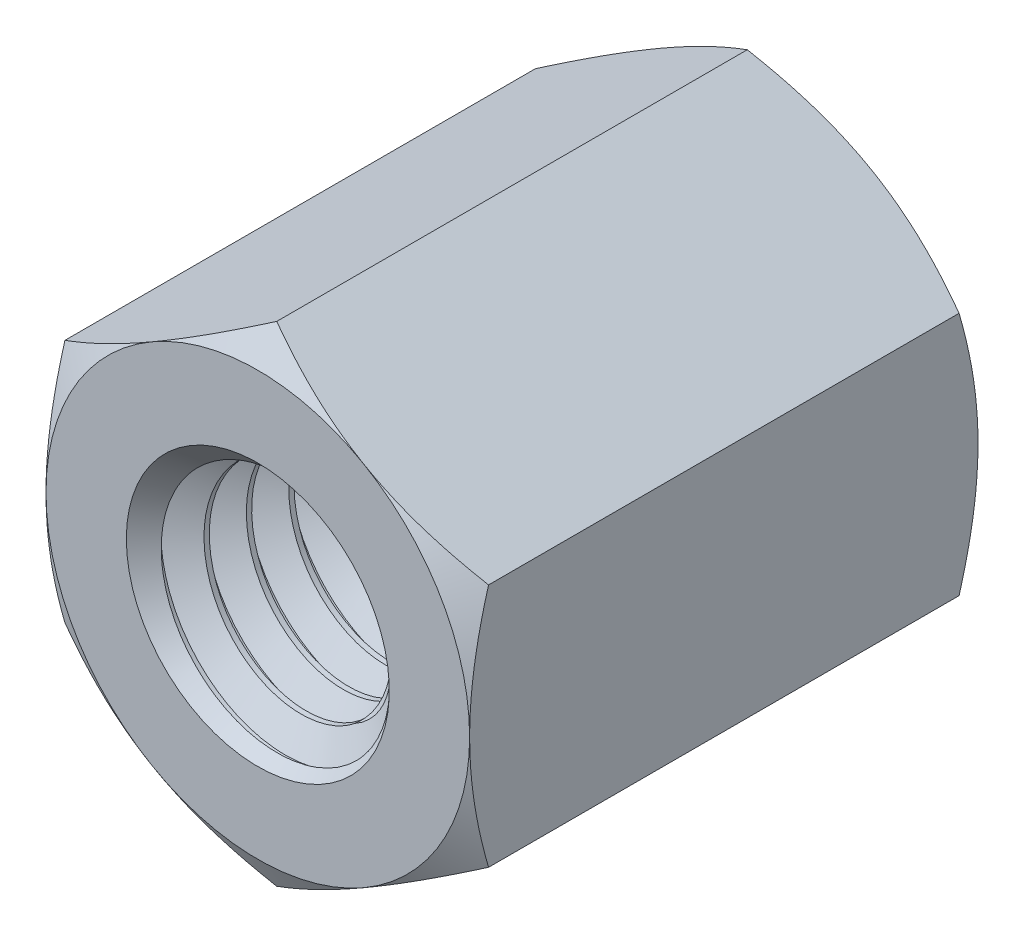
SolidWorks part; units mm, degrees
ref_plane "Front Plane" through (0, 0, 0) normal (0, 0, 1) x (1, 0, 0)
ref_plane "Top Plane" through (0, 0, 0) normal (0, 1, 0) x (1, 0, 0)
ref_plane "Right Plane" through (0, 0, 0) normal (1, 0, 0) x (0, 0, -1)
sketch "Sketch3" plane through (0, 0, 0) normal (1, 0, 0) x (0, 0, -1)
  line L0 (-4.7625, 0) -> (4.7625, 0) construction
  line L1 (0, 3.9688) -> (0, -3.9688) construction
  line L2 (-4.7625, 2.413) -> (-4.7625, -2.413) construction
  point P2 (-7.9375, 0)
  point P3 (7.9375, 0)
  dimension "Length" = 9.525
  dimension "Min Thread Length" = 12.7
  dimension "D1" = 12.7
  dimension "Thread Dia" = 4.826
  dimension "Hex" = 7.9375
sketch "Sketch1" plane through (0, 0, 0) normal (0, 0, 1) x (1, 0, 0)
  line L1 (0, 4.5827) -> (-3.9688, 2.2914)
  line L2 (-3.9688, 2.2914) -> (-3.9688, -2.2914)
  line L3 (-3.9688, -2.2914) -> (0, -4.5827)
  line L4 (0, -4.5827) -> (3.9688, -2.2914)
  line L5 (3.9688, -2.2914) -> (3.9688, 2.2914)
  line L6 (3.9688, 2.2914) -> (0, 4.5827)
  circle A0 centre (0, 0) radius 3.9688 construction
  circle A1 centre (0, 0) radius 2.413
extrude "Extrude1" add sketch "Sketch1" along normal up to vertex (4.7625 mm away) and the other way up to vertex (4.7625 mm away) up to point (0, 0, 4.7625) other way up to point (0, 0, -4.7625)
sketch "Sketch11" plane through (0, 0, -4.7625) normal (0, 0, -1) x (-1, 0, 0)
  circle A0 centre (0, 0) radius 2.413 construction
  circle A1 centre (0, 0) radius 2.413
curve "Helix/Spiral1" pitch 0.7937 height 10.3188 radius 2.413 centre (0, 0, -4.7625) axis (0, 0, 1) start towards (0, 1, 0) parameters "Pitch"=0.7937
sketch "Sketch12" plane through (0, 0, 0) normal (1, 0, 0) x (0, 0, -1)
  line L0 (5.457, 2.413) -> (4.7625, 2.413)
  line L1 (5.457, 2.413) -> (5.1594, 1.8974)
  line L2 (5.1594, 1.8974) -> (5.0602, 1.8974)
  line L3 (5.0602, 1.8974) -> (4.7625, 2.413)
  line L4 (5.1098, 1.8974) -> (5.1098, 2.413) construction
  line L5 (5.3082, 2.1552) -> (4.9113, 2.1552) construction
  dimension "D1" = 0.0992
  dimension "D2" = 0.3969
  dimension "D3" = 60
sweep "Sweep1" add profiles "Sketch12" path "Helix/Spiral1"
sketch "Sketch6" plane through (0, 0, -4.7625) normal (0, 0, -1) x (-1, 0, 0)
  line L6 (0, 4.5827) -> (-3.9688, 2.2914)
  line L7 (-3.9688, 2.2914) -> (-3.9688, -2.2914)
  line L8 (-3.9688, -2.2914) -> (0, -4.5827)
  line L9 (0, -4.5827) -> (3.9688, -2.2914)
  line L10 (3.9688, -2.2914) -> (3.9688, 2.2914)
  line L11 (3.9688, 2.2914) -> (0, 4.5827)
  line L12 (0, 4.5827) -> (-3.9688, 2.2914)
  line L13 (-3.9688, 2.2914) -> (-3.9688, -2.2914)
  line L14 (-3.9688, -2.2914) -> (0, -4.5827)
  line L15 (0, -4.5827) -> (3.9688, -2.2914)
  line L16 (3.9688, -2.2914) -> (3.9688, 2.2914)
  line L17 (3.9688, 2.2914) -> (0, 4.5827)
  dimension "D1" = 0
extrude "Extrude2" cut sketch "Sketch6" along normal through all
sketch "Sketch7" plane through (0, 0, -4.7625) normal (0, 0, -1) x (-1, 0, 0)
  circle A2 centre (0, 0) radius 2.4638
  circle A3 centre (0, 0) radius 2.4638
  dimension "D1" = 0.0508
extrude "Extrude3" cut sketch "Sketch7" against normal through all draft 43
sketch "Sketch8" plane through (0, 0, -4.7625) normal (0, 0, -1) x (-1, 0, 0)
  circle A0 centre (0, 0) radius 3.9688 construction
  circle A1 centre (0, 0) radius 3.9688
extrude "Extrude4" cut sketch "Sketch8" against normal through all draft 60 flip side to cut
mirror "Mirror1" about plane through (0, 0, 0) normal (0, 0, 1) of "Extrude2", "Extrude3", "Extrude4"
sketch "Sketch9" [suppressed] plane through (0, 0, 0) normal (1, 0, 0) x (0, 0, -1)
  line L1 (-12.7, 2.4638) -> (12.7, 2.4638)
  line L2 (-12.7, 2.4638) -> (-12.7, 0)
  line L3 (-12.7, 0) -> (12.7, 0)
  line L4 (12.7, 2.4638) -> (12.7, 0)
  line L7 (-25.4, 0) -> (25.4, 0) construction
revolve "Revolve" [suppressed] add sketch "Sketch9" angle 360 about L0
sketch "Sketch10" [suppressed] plane through (0, 0, 0) normal (1, 0, 0) x (0, 0, -1)
  line L0 (25.4, 2.413) -> (12.7, 2.413)
  line L1 (-25.4, 2.413) -> (-12.7, 2.413)
  line L2 (12.7, 2.413) -> (12.7, -2.413)
  line L3 (-25.4, -2.4638) -> (-12.7, -2.4638)
  line L4 (-12.7, 2.413) -> (-12.7, -2.4638)
  line L5 (12.7, -2.413) -> (25.4, -2.413)
equation "\"D1@Sketch3\" = \"Min Thread Length@Sketch3\""
equation "\"D3@Helix/Spiral1\" = \"Length@Sketch3\"+\"Pitch@Helix/Spiral1\""
equation "\"D1@Sketch12\" = \"Pitch@Helix/Spiral1\"*.125"
equation "\"D2@Sketch12\" = \"Pitch@Helix/Spiral1\"*.5"
